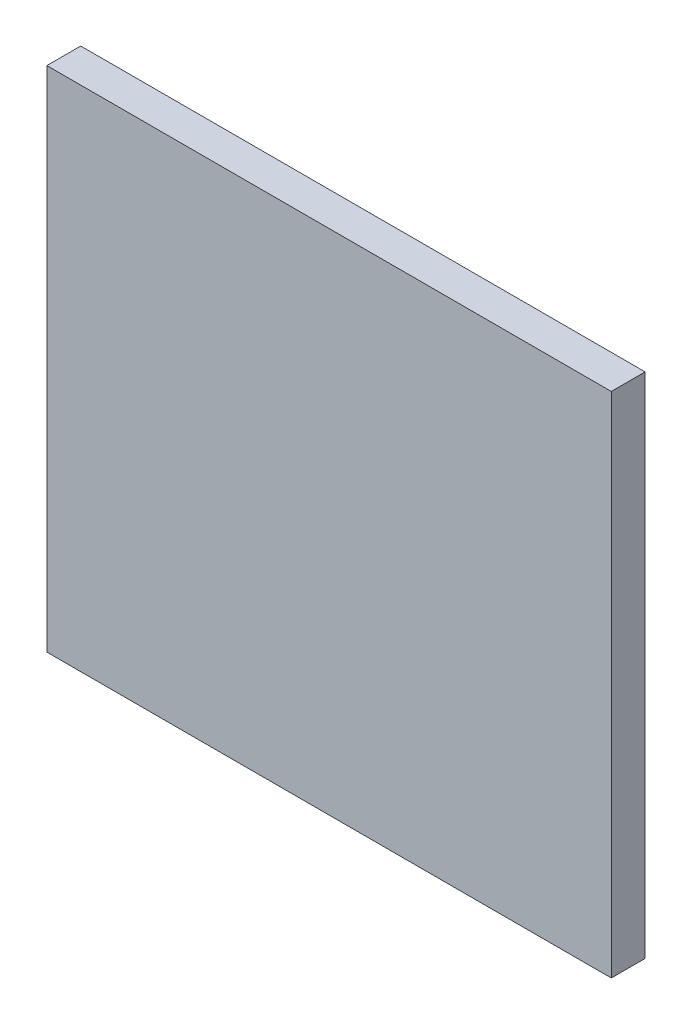
SolidWorks part; units mm, degrees
ref_plane "Front Plane" through (0, 0, 0) normal (0, 0, 1) x (1, 0, 0)
ref_plane "Top Plane" through (0, 0, 0) normal (0, 1, 0) x (1, 0, 0)
ref_plane "Right Plane" through (0, 0, 0) normal (1, 0, 0) x (0, 0, -1)
sketch "Sketch1" plane through (0, 0, 0) normal (0, 0, 1) x (1, 0, 0)
  line L1 (100, -90) -> (-100, -90)
  line L2 (100, -90) -> (100, 90)
  line L3 (100, 90) -> (-100, 90)
  line L4 (-100, -90) -> (-100, 90)
  line L5 (100, -90) -> (-100, 90) construction
  line L6 (100, 90) -> (-100, -90) construction
  point P0 (0, 0)
  dimension "D1" = 180
  dimension "D2" = 200
extrude "Boss-Extrude1" add sketch "Sketch1" along normal blind 12
